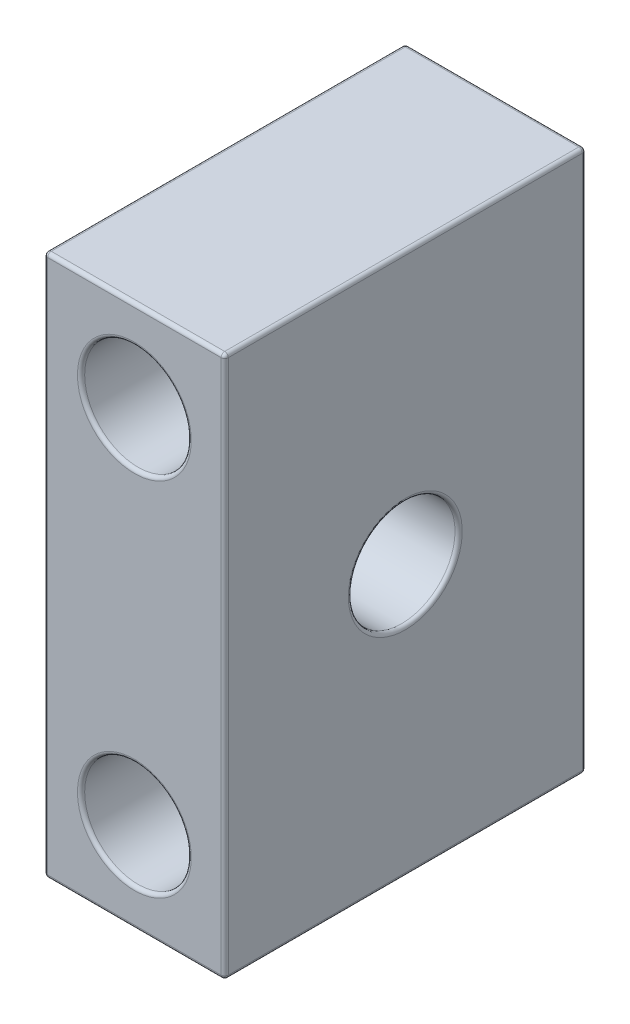
SolidWorks part; units mm, degrees
ref_plane "Front Plane" through (0, 0, 0) normal (0, 0, 1) x (1, 0, 0)
ref_plane "Top Plane" through (0, 0, 0) normal (0, 1, 0) x (1, 0, 0)
ref_plane "Right Plane" through (0, 0, 0) normal (1, 0, 0) x (0, 0, -1)
sketch "Sketch1" plane through (0, 0, 0) normal (0, 0, 1) x (1, 0, 0)
  line L1 (0, 0) -> (25.4, 0)
  line L2 (0, 0) -> (0, 76.2)
  line L3 (0, 76.2) -> (25.4, 76.2)
  line L4 (25.4, 0) -> (25.4, 76.2)
  dimension "D1" = 76.2
  dimension "D2" = 25.4
extrude "Extrude1" add sketch "Sketch1" along normal blind 50.8
hole_wizard "Ø15.0 (15) Diameter Hole1" positions "3DSketch1" profile "Sketch2" hole size "Ø15.0" standard "Ansi Metric" end condition up to next
sketch3d "3DSketch1"
  line L0 (25.4, 76.2, 50.8) -> (0, 76.2, 50.8) construction
  line L1 (0, 76.2, 50.8) -> (0, 0, 50.8) construction
  line L2 (0, 0, 50.8) -> (25.4, 0, 50.8) construction
  point P0 (12.7, 63.5, 50.8)
  point P2 (12.7, 12.7, 50.8)
  dimension "D1" = 12.7
  dimension "D2" = 12.7
  dimension "D3" = 12.7
  dimension "D4" = 12.7
sketch "Sketch2" plane through (12.7, 63.5, 50.8) normal (1, 0, 0) x (0, -1, 0)
  line L0 (0, 0) -> (0, 50.8)
  line L1 (0, 50.8) -> (7.5, 50.8)
  line L2 (7.5, 50.8) -> (7.5, 0)
  line L5 (7.5, 0) -> (0, 0)
  line L11 (0, -6.35) -> (0, 107.95) construction
  dimension "Thru Hole Dia." = 15
  dimension "Thru Hole Depth" = 50.8
hole_wizard "Ø15.0 (15) Diameter Hole3" positions "3DSketch3" profile "Sketch4" hole size "Ø15.0" standard "Ansi Metric" end condition up to next
sketch3d "3DSketch3"
  line L0 (25.4, 0, 50.8) -> (25.4, 76.2, 50.8) construction
  line L1 (25.4, 76.2, 50.8) -> (25.4, 76.2, 0) construction
  point P0 (25.4, 38.1, 25.4)
  dimension "D1" = 25.4
  dimension "D2" = 38.1
sketch "Sketch4" plane through (25.4, 38.1, 25.4) normal (0, 1, 0) x (0, 0, -1)
  line L0 (0, 0) -> (0, 25.4)
  line L1 (0, 25.4) -> (7.5, 25.4)
  line L2 (7.5, 25.4) -> (7.5, 0)
  line L5 (7.5, 0) -> (0, 0)
  line L11 (0, -6.35) -> (0, 107.95) construction
  dimension "Thru Hole Dia." = 15
  dimension "Thru Hole Depth" = 25.4
fillet "Fillet1" radius 0.508 18 edges at (0, 0, 25.4) (0, 38.1, 17.9) (12.7, 0, 0) (0, 38.1, 0) (5.2, 12.7, 0) (5.2, 63.5, 0) (0, 76.2, 25.4) (12.7, 76.2, 0) (25.4, 38.1, 17.9) (25.4, 0, 25.4) (25.4, 76.2, 25.4) (25.4, 38.1, 0) (12.7, 76.2, 50.8) (25.4, 38.1, 50.8) (12.7, 0, 50.8) (0, 38.1, 50.8) (20.2, 12.7, 50.8) (20.2, 63.5, 50.8)
